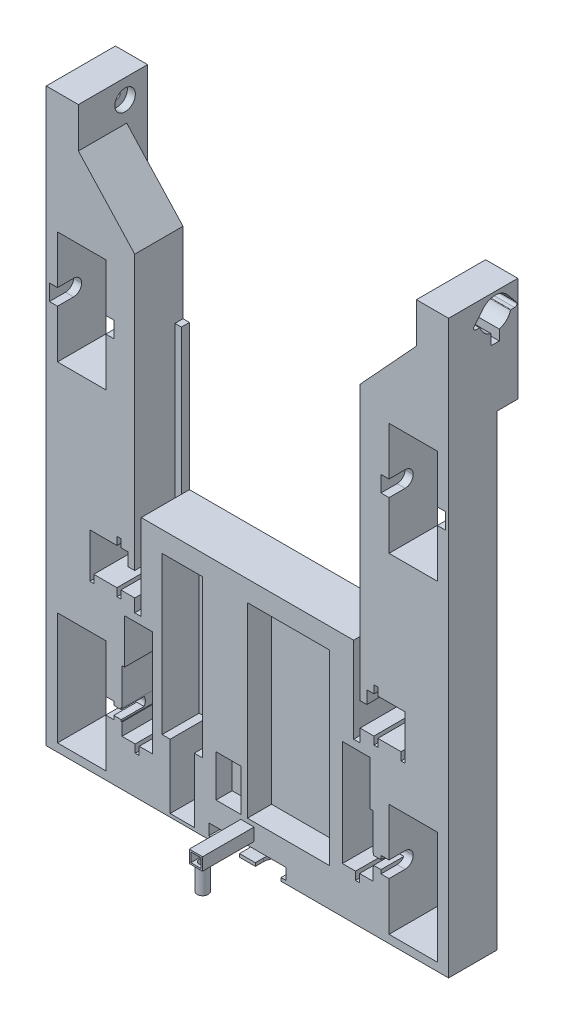
SolidWorks part; units mm, degrees
ref_plane "Front Plane" through (0, 0, 0) normal (0, 0, 1) x (1, 0, 0)
ref_plane "Top Plane" through (0, 0, 0) normal (0, 1, 0) x (1, 0, 0)
ref_plane "Right Plane" through (0, 0, 0) normal (1, 0, 0) x (0, 0, -1)
sketch "Sketch1" plane through (0, 0, 0) normal (0, 0, 1) x (1, 0, 0)
  line L1 (0, 0) -> (250, 0)
  line L8 (0, 0) -> (0, 330)
  line L9 (0, 330) -> (250, 330)
  line L10 (250, 330) -> (250, 0)
  dimension "D1" = 250
  dimension "D2" = 250
  dimension "D3" = 330
extrude "Boss-Extrude2" add sketch "Sketch1" along normal blind 30
sketch "Sketch2" plane through (0, 0, 30) normal (0, 0, 1) x (1, 0, 0)
  line L1 (7, 5) -> (37, 5)
  line L3 (7, 75) -> (37, 75)
  line L4 (37, 5) -> (37, 35)
  line L9 (7, 75) -> (7, 5)
  line L10 (37, 45) -> (42, 45)
  line L12 (37, 35) -> (42, 35)
  line L13 (42, 45) -> (42, 42.675)
  line L14 (42, 37.325) -> (42, 35)
  line L15 (0, 330) -> (0, 0) construction
  line L16 (42, 42.675) -> (46.6, 42.675)
  line L18 (42, 37.325) -> (46.6, 37.325)
  line L19 (46.6, 42.675) -> (46.6, 37.325)
  line L20 (37, 45) -> (37, 75)
  line L21 (7, 40) -> (46.6, 40) construction
  line L22 (0, 0) -> (250, 0) construction
  line L23 (56.55, 94.3) -> (56.55, 23.6) construction
  line L24 (47.1, 28.6) -> (66, 28.6)
  line L25 (47.1, 28.6) -> (47.1, 36.25)
  line L26 (47.1, 66.6) -> (66, 66.6)
  line L27 (66, 28.6) -> (66, 66.6)
  line L28 (48.7, 66.6) -> (66, 66.6)
  line L29 (48.7, 66.6) -> (48.7, 94.3)
  line L30 (48.7, 94.3) -> (66, 94.3)
  line L31 (66, 66.6) -> (66, 94.3)
  line L32 (125, 330) -> (125, 0) construction
  line L33 (55.3, 28.6) -> (57.8, 28.6)
  line L34 (55.3, 28.6) -> (55.3, 23.6)
  line L35 (55.3, 23.6) -> (57.8, 23.6)
  line L36 (57.8, 28.6) -> (57.8, 23.6)
  line L41 (47.1, 43.75) -> (46.6, 43.75)
  line L43 (47.1, 36.25) -> (46.6, 36.25)
  line L44 (47.1, 66.6) -> (47.1, 43.75)
  line L45 (46.6, 43.75) -> (46.6, 36.25)
  line L47 (203.4, 43.75) -> (203.4, 36.25)
  line L48 (202.9, 66.6) -> (202.9, 43.75)
  line L49 (202.9, 36.25) -> (203.4, 36.25)
  line L50 (202.9, 43.75) -> (203.4, 43.75)
  line L51 (192.2, 28.6) -> (192.2, 23.6)
  line L52 (194.7, 23.6) -> (192.2, 23.6)
  line L53 (194.7, 28.6) -> (194.7, 23.6)
  line L54 (194.7, 28.6) -> (192.2, 28.6)
  line L55 (184, 66.6) -> (184, 94.3)
  line L56 (201.3, 94.3) -> (184, 94.3)
  line L57 (201.3, 66.6) -> (201.3, 94.3)
  line L58 (201.3, 66.6) -> (184, 66.6)
  line L60 (202.9, 66.6) -> (184, 66.6)
  line L61 (202.9, 28.6) -> (202.9, 36.25)
  line L62 (202.9, 28.6) -> (184, 28.6)
  line L63 (213, 45) -> (213, 75)
  line L64 (203.4, 42.675) -> (203.4, 37.325)
  line L65 (208, 37.325) -> (203.4, 37.325)
  line L66 (208, 42.675) -> (203.4, 42.675)
  line L67 (208, 37.325) -> (208, 35)
  line L68 (208, 45) -> (208, 42.675)
  line L69 (213, 35) -> (208, 35)
  line L70 (213, 45) -> (208, 45)
  line L71 (243, 75) -> (243, 5)
  line L72 (213, 5) -> (213, 35)
  line L73 (243, 75) -> (213, 75)
  line L74 (243, 5) -> (213, 5)
  line L75 (184, 66.6) -> (184, 28.6)
  line L76 (250, 330) -> (0, 330) construction
  line L77 (0, 165) -> (250, 165) construction
  line L78 (250, 0) -> (250, 330) construction
  line L97 (228, 280) -> (228, 210) construction
  line L101 (37, 280) -> (37, 210)
  line L103 (7, 280) -> (7, 210)
  line L104 (2, 240) -> (7, 240)
  line L105 (2, 250) -> (2, 240)
  line L106 (7, 250) -> (2, 250)
  line L108 (22, 280) -> (22, 210) construction
  line L111 (37, 250) -> (42, 250)
  line L112 (7, 210) -> (37, 210)
  line L113 (7, 280) -> (37, 280)
  line L114 (0, 0) -> (250, 0) construction
  line L115 (101, 9) -> (149, 9)
  line L116 (101, 9) -> (101, 2)
  line L117 (101, 2) -> (149, 2)
  line L118 (149, 9) -> (149, 2)
  line L119 (125, 2) -> (125, 9) construction
  line L120 (101, 5.5) -> (149, 5.5) construction
  line L121 (92, 2) -> (92, 42)
  line L122 (176, 23.5) -> (125, 23.5)
  line L123 (176, 23.5) -> (176, 139.5)
  line L124 (176, 139.5) -> (125, 139.5)
  line L125 (125, 23.5) -> (125, 139.5)
  line L127 (97, 42) -> (97, 139.5)
  line L128 (97, 139.5) -> (72, 139.5)
  line L129 (72, 42) -> (72, 139.5)
  line L132 (77, 42) -> (92, 42)
  line L134 (84.5, 42) -> (84.5, 2) construction
  line L135 (77, 2) -> (92, 2)
  line L136 (72, 42) -> (97, 42)
  line L137 (77, 2) -> (77, 42)
  line L138 (208, 240) -> (213, 240)
  line L139 (120.875, 20.8) -> (129.125, 20.8)
  line L140 (120.875, 20.8) -> (120.875, 13)
  line L141 (120.875, 13) -> (129.125, 13)
  line L142 (129.125, 20.8) -> (129.125, 13)
  line L143 (125, 13) -> (125, 20.8) construction
  line L144 (120.875, 16.9) -> (129.125, 16.9) construction
  line L145 (208, 250) -> (208, 240)
  line L146 (243, 280) -> (213, 280)
  line L147 (243, 210) -> (213, 210)
  line L148 (213, 250) -> (208, 250)
  line L149 (243, 250) -> (248, 250)
  line L153 (248, 250) -> (248, 240)
  line L154 (248, 240) -> (243, 240)
  line L155 (243, 280) -> (243, 210)
  line L157 (42, 250) -> (42, 240)
  line L158 (42, 240) -> (37, 240)
  line L159 (213, 280) -> (213, 210)
  line L169 (46.39, 129.71) -> (50.8, 129.71)
  line L170 (27.05, 129.71) -> (43.93, 129.71)
  line L171 (27.05, 129.71) -> (27.05, 107)
  line L172 (29.54, 107) -> (43.94, 107)
  line L173 (50.8, 129.71) -> (50.8, 121.74)
  line L175 (43.93, 129.71) -> (43.93, 134.62)
  line L176 (43.93, 134.62) -> (46.39, 134.62)
  line L177 (46.39, 129.71) -> (46.39, 134.62)
  line L179 (43.94, 107) -> (43.94, 102.13)
  line L180 (43.94, 102.13) -> (46.4, 102.13)
  line L181 (46.4, 107) -> (46.4, 102.13)
  line L183 (29.54, 107) -> (29.54, 102)
  line L184 (29.54, 102) -> (27.05, 102)
  line L185 (27.05, 107) -> (27.05, 102)
  line L186 (46.4, 107) -> (55, 107)
  line L188 (50.8, 121.74) -> (55, 121.74)
  line L189 (55, 107) -> (55, 121.74)
  line L191 (195, 107) -> (195, 121.74)
  line L192 (199.2, 121.74) -> (195, 121.74)
  line L193 (203.6, 107) -> (195, 107)
  line L194 (222.95, 107) -> (222.95, 102)
  line L195 (220.46, 102) -> (222.95, 102)
  line L196 (220.46, 107) -> (220.46, 102)
  line L197 (203.6, 107) -> (203.6, 102.13)
  line L198 (206.06, 102.13) -> (203.6, 102.13)
  line L199 (206.06, 107) -> (206.06, 102.13)
  line L200 (203.61, 129.71) -> (203.61, 134.62)
  line L201 (206.07, 134.62) -> (203.61, 134.62)
  line L202 (206.07, 129.71) -> (206.07, 134.62)
  line L203 (199.2, 129.71) -> (199.2, 121.74)
  line L204 (220.46, 107) -> (206.06, 107)
  line L205 (222.95, 129.71) -> (222.95, 107)
  line L206 (222.95, 129.71) -> (206.07, 129.71)
  line L207 (203.61, 129.71) -> (199.2, 129.71)
  line L208 (213, 45) -> (213, 35)
  line L209 (121, 23.5) -> (105.5, 23.5)
  line L210 (121, 23.5) -> (121, 49.5)
  line L211 (121, 49.5) -> (105.5, 49.5)
  line L212 (105.5, 23.5) -> (105.5, 49.5)
  line L213 (37, 45) -> (37, 35)
  line L214 (20, 330) -> (55, 292)
  line L215 (2, 292) -> (50, 292)
  line L216 (2, 292) -> (2, 285)
  line L217 (2, 285) -> (50, 285)
  line L218 (50, 292) -> (50, 285)
  line L219 (26, 285) -> (26, 292) construction
  line L220 (2, 288.5) -> (50, 288.5) construction
  line L224 (55, 292) -> (55, 242.25)
  line L225 (55, 242.25) -> (195, 242.25)
  line L226 (230, 330) -> (20, 330)
  line L228 (55, 107) -> (55, 121.74)
  line L231 (230, 330) -> (195, 292)
  line L235 (195, 107) -> (195, 121.74)
  line L236 (195, 292) -> (195, 242.25)
  line L237 (55, 107) -> (55, 99)
  line L238 (55, 242.25) -> (59, 242.25)
  line L239 (55, 242.25) -> (55, 107)
  line L240 (55, 107) -> (59, 107)
  line L241 (59, 242.25) -> (59, 107)
  line L242 (55, 99) -> (59, 99)
  line L243 (59, 99) -> (59, 107)
  line L244 (55, 119.24) -> (59, 119.24)
  line L245 (191, 119.24) -> (195, 119.24)
  line L246 (195, 242.25) -> (195, 107)
  line L247 (191, 242.25) -> (191, 107)
  line L248 (195, 107) -> (191, 107)
  line L249 (191, 99) -> (191, 107)
  line L250 (195, 99) -> (191, 99)
  line L251 (195, 107) -> (195, 99)
  line L252 (0, 311.75) -> (250, 311.75) construction
  line L253 (59, 152.2754) -> (191, 152.2754)
  line L254 (191, 152.2754) -> (191, 242.25)
  line L255 (59, 242.25) -> (59, 152.2754)
  point P26 (56.55, 28.6)
  point P64 (125, 330)
  point P92 (125, 5.5)
  point P101 (2, 245)
  point P110 (84.5, 2)
  point P112 (125, 16.9)
  point P133 (43.93, 132.165)
  point P159 (26, 288.5)
  point P179 (125, 242.25)
  dimension "D1" = 7
  dimension "D2" = 5
  dimension "D3" = 70
  dimension "D5" = 10
  dimension "D6" = 5
  dimension "D7" = 30
  dimension "D8" = 5.35
  dimension "D9" = 4.6
  dimension "D10" = 27.7
  dimension "D11" = 7.5
  dimension "D12" = 0.5
  dimension "D13" = 18.9
  dimension "D14" = 2.5
  dimension "D15" = 3.75
  dimension "D16" = 5
  dimension "D17" = 70.7
  dimension "D18" = 22.85
  dimension "D19" = 17.3
  dimension "D20" = 1.6
  dimension "D21" = 30
  dimension "D22" = 70
  dimension "D23" = 48
  dimension "D24" = 7
  dimension "D25" = 2
  dimension "D26" = 51
  dimension "D27" = 116
  dimension "D28" = 14.5
  dimension "D29" = 25
  dimension "D30" = 97.5
  dimension "D31" = 15
  dimension "D32" = 40
  dimension "D33" = 2
  dimension "D34" = 6
  dimension "D35" = 12.5
  dimension "D36" = 7.8
  dimension "D37" = 8.25
  dimension "D38" = 4
  dimension "D39" = 10
  dimension "D40" = 35
  dimension "D41" = 50
  dimension "D42" = 7
  dimension "D43" = 5
  dimension "D44" = 23.75
  dimension "D45" = 22.71
  dimension "D46" = 5
  dimension "D47" = 2.49
  dimension "D48" = 14.4
  dimension "D49" = 4.87
  dimension "D50" = 2.46
  dimension "D51" = 2.46
  dimension "D52" = 4.91
  dimension "D53" = 16.88
  dimension "D54" = 4.2
  dimension "D55" = 27
  dimension "D56" = 17
  dimension "D57" = 14.74
  dimension "D58" = 26
  dimension "D59" = 15.5
  dimension "D60" = 4
  dimension "D61" = 48
  dimension "D62" = 7
  dimension "D63" = 5
  dimension "D64" = 2
  dimension "D65" = 20
  dimension "D66" = 38
  dimension "D67" = 13
  dimension "D68" = 140
  dimension "D69" = 8
  dimension "D70" = 2.5
  dimension "D71" = 2.5
  dimension "D72" = 18.25
  dimension "D73" = 49.75
sketch "US" plane through (0, 0, 0) normal (0, -1, 0) x (1, 0, 0)
  line L0 (101, 30) -> (149, 30) construction
  line L2 (101, 30) -> (101, 15) construction
  line L3 (101, 15) -> (149, 15) construction
  line L4 (149, 30) -> (149, 15) construction
  line L5 (104.075, 25) -> (104.075, 30)
  line L6 (101, 30) -> (149, 30) construction
  line L7 (120.075, 25) -> (120.075, 30)
  line L8 (125, 30) -> (125, 15) construction
  line L9 (129.925, 25) -> (129.925, 30)
  line L10 (145.925, 25) -> (145.925, 30)
  arc A0 (104.075, 25) -> (120.075, 25) centre (112.075, 25) ccw
  arc A1 (145.925, 25) -> (129.925, 25) centre (137.925, 25) cw
  point P0 (125, 30)
  point P4 (112.075, 17)
  line M10 (250, 30) -> (0, 30)
  dimension "D3" = 16
  dimension "D1" = 48
  dimension "D2" = 15
  dimension "D4" = 2
  dimension "D5" = 25.85
extrude "Boss-Extrude4" add sketch "Sketch2" along normal blind 32 contours L140 L139 L142 L141
sketch "Sketch6" plane through (0, 0, 62) normal (0, 0, 1) x (1, 0, 0)
  line L8 (121.875, 14) -> (128.125, 14)
  line L9 (128.125, 14) -> (128.125, 19.8)
  line L10 (128.125, 19.8) -> (121.875, 19.8)
  line L11 (121.875, 19.8) -> (121.875, 14)
  line L12 (121.875, 14) -> (128.125, 14)
  line L13 (128.125, 14) -> (128.125, 19.8)
  line L14 (128.125, 19.8) -> (121.875, 19.8)
  line L15 (121.875, 19.8) -> (121.875, 14)
  dimension "D1" = 1
extrude "Cut-Extrude1" cut sketch "Sketch6" against normal blind 7
sketch "Sketch7" plane through (0, 13, 0) normal (0, -1, 0) x (1, 0, 0)
  line L0 (120.875, 55) -> (129.125, 55) construction
  line L1 (120.875, 62) -> (120.875, 30) construction
  line L2 (129.125, 62) -> (129.125, 30) construction
  line L3 (120.875, 62) -> (129.125, 62) construction
  circle A0 centre (125, 57.76) radius 2.4
  point P10 (125, 55)
  dimension "D2" = 4.8
  dimension "D1" = 7
  dimension "D3" = 2.76
extrude "Cut-Extrude2" cut sketch "Sketch7" against normal blind 1 contours A0
extrude "Ultrasonic Sensor Eyes" cut sketch "US" against normal blind 2 contours L5 A0 L7 M10 | A1 L10 L9 M10 region at (137.925, 0, 24.2171) region at (112.075, 0, 24.2171)
extrude "Wheel Holes" cut sketch "Sketch2<5>" against normal through all contours L13 L10 L20 L3 L9 L1 L4 L12 L14 | L68 L67 L69 L72 L74 L71 L73 L63 L70 | L146 L159 L147 L155 | L113 L103 L112 L101 region at (22, 40, 30) region at (228, 40, 30) region at (22, 245, 30) region at (228, 245, 30)
sketch "Sketch2<5>" plane through (0, 0, 30) normal (0, 0, 1) x (1, 0, 0) same geometry as "Sketch2"
extrude "Ultrasonic Sensor " cut sketch "Sketch2<6>" against normal blind 15 contours L118 L115 L116 L117 region at (125, 5.5, 30)
sketch "Sketch2<6>" plane through (0, 0, 30) normal (0, 0, 1) x (1, 0, 0) same geometry as "Sketch2"
extrude "Cut-Extrude5" cut sketch "Sketch2<7>" against normal blind 23 contours L129 L136 L132 L127 L128 | L137 L135 L121 L132 region at (84.5, 22, 30) region at (84.5, 90.75, 30)
sketch "Sketch2<7>" plane through (0, 0, 30) normal (0, 0, 1) x (1, 0, 0) same geometry as "Sketch2"
extrude "Cut-Extrude6" cut sketch "Sketch2<9>" against normal blind 15 contours L124 L125 L122 L123
sketch "Sketch2<9>" plane through (0, 0, 30) normal (0, 0, 1) x (1, 0, 0) same geometry as "Sketch2"
extrude "Cut-Extrude7" cut sketch "Sketch2<10>" against normal blind 10 contours L211 L212 L209 L210
sketch "Sketch2<10>" plane through (0, 0, 30) normal (0, 0, 1) x (1, 0, 0) same geometry as "Sketch2"
extrude "Extrude-Thin3" add sketch "Sketch7<5>" along normal blind 15 thin thin type one direction wall 1
sketch "Sketch7<5>" plane through (0, 13, 0) normal (0, -1, 0) x (1, 0, 0) same geometry as "Sketch7"
extrude "Cut-Extrude8" cut sketch "Sketch2<11>" against normal blind 21.25 contours L26 L31 L30 L29 | L41 L45 L19 L43 L25 L24 L27 L26 L44 | L58 L57 L56 L55 | L58 L75 L62 L54 L61 L49 L47 L50 L48 L60 | L53 L54 L51 L52 | L34 L35 L36 L33 region at (56.4996, 47.5605, 30) region at (57.35, 80.45, 30) region at (193.5004, 47.5605, 30) region at (192.65, 80.45, 30) region at (193.45, 26.1, 30)
sketch "Sketch2<11>" plane through (0, 0, 30) normal (0, 0, 1) x (1, 0, 0) same geometry as "Sketch2"
extrude "Cut-Extrude9" cut sketch "Sketch2<12>" against normal blind 15 and the other way through all contours L10 L213 L12 L14 L18 L19 L16 L13 | L208 L70 L68 L66 L47 L65 L67 L69 | L159 L148 L145 L138 | L149 L155 L154 L153 | L103 L106 L105 L104 | L158 L157 L111 L101 region at (41.0833, 40, 30) region at (208.9167, 40, 30) region at (39.5, 245, 30) region at (4.5, 245, 30) region at (210.5, 245, 30) region at (245.5, 245, 30)
sketch "Sketch2<12>" plane through (0, 0, 30) normal (0, 0, 1) x (1, 0, 0) same geometry as "Sketch2"
extrude "Cut-Extrude11" cut sketch "Sketch2<14>" against normal blind 25 contours L186 L189 L239 L188 L173 L169 L177 L176 L175 L170 L171 L185 L184 L183 L172 L179 L180 L181 | L239 L244 L241 L225 | L225 L247 L245 L235 L246 | L200 L207 L203 L192 L235 L191 L193 L197 L198 L199 L204 L196 L195 L194 L205 L206 L202 L201 region at (40.3094, 117.7002, 30) region at (57, 180.745, 30) region at (193, 180.745, 30) region at (209.6906, 117.7002, 30)
sketch "Sketch2<14>" plane through (0, 0, 30) normal (0, 0, 1) x (1, 0, 0) same geometry as "Sketch2"
sketch "Sketch8" plane through (250, 0, 0) normal (1, 0, 0) x (0, 0, -1)
  line L0 (-1.0005, 352.9) -> (-1.0005, 332.0358) construction
  line L7 (-8.5368, 349.4198) -> (-14.1674, 342.556)
  line L8 (-13.0819, 340.2616) -> (-10.7815, 340.2616)
  line L9 (11.0809, 340.2616) -> (8.7804, 340.2616)
  line L12 (19.5, 330) -> (19.5, 355) construction
  line L15 (6.5358, 349.4198) -> (12.1664, 342.556)
  line L16 (-13.0819, 341.6656) -> (-12.7619, 341.6656) construction
  line L17 (-13.0819, 342.4956) -> (-12.7619, 342.4956)
  line L18 (-13.0819, 340.8356) -> (-12.7619, 340.8356)
  line L19 (5.3495, 343) -> (19.5, 343) construction
  line L20 (11.0809, 341.6656) -> (10.7609, 341.6656) construction
  line L21 (11.0809, 342.4956) -> (10.7609, 342.4956)
  line L22 (11.0809, 340.8356) -> (10.7609, 340.8356)
  line L26 (1.4995, 333.4209) -> (1.4995, 327.0358)
  line L27 (1.4995, 327.0358) -> (-3.5005, 327.0358)
  line L28 (-3.5005, 333.4209) -> (-3.5005, 327.0358)
  line L31 (0, 290) -> (13, 290)
  line L32 (13, 293.9869) -> (13, 290)
  line L33 (-30, 330) -> (-30, 355)
  line L34 (-30, 355) -> (13, 355)
  line L35 (13, 355) -> (13, 293.9869)
  line L36 (-30, 330) -> (0, 330)
  line L37 (0, 330) -> (0, 290)
  arc A0 (-10.4383, 340.0103) -> (-10.7815, 340.2616) centre (-10.7815, 339.9016) ccw
  arc A2 (-13.0819, 340.2616) -> (-14.1674, 342.556) centre (-13.0819, 341.6656) cw
  circle A7 centre (-1.0005, 343) radius 2
  arc A8 (6.5358, 349.4198) -> (-8.5368, 349.4198) centre (-1.0005, 343) ccw
  arc A10 (-10.4383, 340.0103) -> (8.4372, 340.0103) centre (-1.0005, 343) ccw
  arc A19 (11.0809, 340.2616) -> (12.1664, 342.556) centre (11.0809, 341.6656) ccw
  arc A20 (8.4372, 340.0103) -> (8.7804, 340.2616) centre (8.7804, 339.9016) cw
  arc A21 (-13.0819, 342.4956) -> (-13.0819, 340.8356) centre (-13.0819, 341.6656) ccw
  arc A22 (-12.7619, 340.8356) -> (-12.7619, 342.4956) centre (-12.7619, 341.6656) ccw
  arc A23 (11.0809, 342.4956) -> (11.0809, 340.8356) centre (11.0809, 341.6656) cw
  arc A24 (10.7609, 340.8356) -> (10.7609, 342.4956) centre (10.7609, 341.6656) cw
  circle A26 centre (-15, 330) radius 34.5 construction
  point P5 (-14.351, 341.0651)
  point P8 (-12.9219, 341.6656)
  point P10 (12.35, 341.0651)
  point P18 (10.9209, 341.6656)
  line M38 (0, 0) -> (0, 330)
  line M39 (0, 330) -> (-30, 330)
  dimension "D1" = 9.9
  dimension "D2" = 9.9
  dimension "D3" = 0.83
  dimension "D6" = 0.36
  dimension "D8" = 1.404
  dimension "D13" = 0.32
  dimension "D12" = 4
  dimension "D15" = 69
  dimension "D16" = 13
  dimension "D18" = 0.65
  dimension "D4" = 8.8778
  dimension "D7" = 2.3004
  dimension "D9" = 26.701
  dimension "D10" = 13
  dimension "D11" = 5
  dimension "D14" = 5
  dimension "D17" = 25
  dimension "D19" = 65
  dimension "D20" = 14.1505
extrude "Boss-Extrude5" add sketch "Sketch8<6>" against normal blind 20 contours A20 A10 L26 L27 L31 L32 L35 L34 L33 L36 L28 A0 L8 A2 L7 A8 L15 A19 L9 M38 M39 | A10 A20 L9 A19 L15 A8 L7 A2 L8 A0 A22 L18 A21 L17 A7 L22 A24 L21 A23 | A10 L28 L27 L26 M39 M38 | L18 A22 L17 A21 | A7 | A24 L22 A23 L21 region at (250, 352.5654, 1.0005) region at (250, 346.4822, 11.9547) region at (250, 330.9345, 0.6206) region at (250, 341.6656, 12.9219) region at (250, 341.6656, -10.9209) region at (250, 343, 1.0005)
sketch "Sketch8<6>" plane through (250, 0, 0) normal (1, 0, 0) x (0, 0, -1) same geometry as "Sketch8"
extrude "Boss-Extrude6" add sketch "Sketch8<7>" against normal blind 20 from offset 230 contours A20 A10 L26 L27 L31 L32 L35 L34 L33 L36 L28 A0 L8 A2 L7 A8 L15 A19 L9 M38 M39 | A10 A20 L9 A19 L15 A8 L7 A2 L8 A0 A22 L18 A21 L17 A7 L22 A24 L21 A23 | A7 | L18 A22 L17 A21 | A24 L22 A23 L21 | A10 L28 L27 L26 M39 M38 | L28 L27 M39 M38 region at (250, 352.5654, 1.0005) region at (250, 346.4822, 11.9547) region at (250, 330.9345, 0.6206) region at (250, 328.5179, 1.7503) region at (250, 341.6656, 12.9219) region at (250, 341.6656, -10.9209) region at (250, 343, 1.0005) offset against normal yes
sketch "Sketch8<7>" plane through (250, 0, 0) normal (1, 0, 0) x (0, 0, -1) same geometry as "Sketch8"
extrude "Cut-Extrude12" cut sketch "Sketch8" against normal blind 15 contours A10 A20 L9 A19 L15 A8 L7 A2 L8 A0 A22 L18 A21 L17 A7 L22 A24 L21 A23 | A10 L28 L27 L26 | L28 L27 M39 M38 region at (250, 352.5654, 1.0005) region at (250, 330.9345, 0.6206) region at (250, 328.5179, 1.7503)
extrude "Cut-Extrude13" cut sketch "Sketch8<4>" against normal blind 18 contours L18 A22 L17 A21 | A24 L22 A23 L21 region at (250, 341.6656, 12.9219) region at (250, 341.6656, -10.9209)
sketch "Sketch8<4>" plane through (250, 0, 0) normal (1, 0, 0) x (0, 0, -1) same geometry as "Sketch8"
extrude "Cut-Extrude14" cut sketch "Sketch8<5>" against normal through all contours A7 region at (250, 343, 1.0005)
sketch "Sketch8<5>" plane through (250, 0, 0) normal (1, 0, 0) x (0, 0, -1) same geometry as "Sketch8"
extrude "Cut-Extrude17" cut sketch "Sketch2<16>" against normal through all contours L214 L224 L225 L236 L231 L226
sketch "Sketch2<16>" plane through (0, 0, 30) normal (0, 0, 1) x (1, 0, 0) same geometry as "Sketch2"
extrude "Extrude-Thin4" add sketch "Sketch2<17>" along normal blind 15 thin contours L215 L218 L217 L216 thin type one direction wall 1
sketch "Sketch2<17>" plane through (0, 0, 30) normal (0, 0, 1) x (1, 0, 0) same geometry as "Sketch2"
sketch "Sketch13" plane through (0, 293, 0) normal (0, 1, 0) x (1, 0, 0)
  line L0 (49, -45) -> (1, -45) construction
  line L1 (49, -45) -> (49, -30) construction
  line L2 (49, -30) -> (1, -30) construction
  line L3 (1, -45) -> (1, -30) construction
  line L4 (45.925, -40) -> (45.925, -45)
  line L5 (49, -45) -> (1, -45) construction
  line L6 (29.925, -40) -> (29.925, -45)
  line L7 (25, -45.6477) -> (25, -30) construction
  line L8 (20.075, -40) -> (20.075, -45)
  line L9 (4.075, -40) -> (4.075, -45)
  line L10 (1, -45) -> (51, -45) construction
  line L11 (1, -45) -> (1, -30) construction
  arc A0 (45.925, -40) -> (29.925, -40) centre (37.925, -40) ccw
  arc A1 (4.075, -40) -> (20.075, -40) centre (12.075, -40) cw
  line M5 (1, -45) -> (51, -45)
  dimension "D2" = 8
  dimension "D1" = 15
  dimension "D3" = 5
  dimension "D4" = 25.85
  dimension "D5" = 48
extrude "Cut-Extrude18" cut sketch "Sketch13" against normal blind 1 contours A1 L9 L8 M5 | L4 A0 L6 M5 region at (12.075, 293, 39.2171) region at (37.925, 293, 39.2171)
fillet "Fillet2" radius 5 12 edges at (39.5, 45, 15) (39.5, 35, 15) (210.5, 35, 15) (210.5, 45, 15) (210.5, 250, 15) (245.5, 250, 15) (245.5, 240, 15) (210.5, 240, 15) (4.5, 240, 15) (4.5, 250, 15) (39.5, 240, 15) (39.5, 250, 15)
extrude "Cut-Extrude19" cut sketch "Sketch2<18>" against normal through all contours L244 L189 L240 L241 | L242 L243 L240 L237 | L248 L191 L245 L247 | L251 L248 L249 L250 region at (57, 113.12, 30) region at (57, 103, 30) region at (193, 113.12, 30) region at (193, 103, 30)
sketch "Sketch2<18>" plane through (0, 0, 30) normal (0, 0, 1) x (1, 0, 0) same geometry as "Sketch2"
sketch "Sketch15" plane through (230, 0, 0) normal (-1, 0, 0) x (0, 0, 1)
  circle A0 centre (1.0005, 343) radius 6.39
  circle A1 centre (1.0005, 343) radius 0.9
  dimension "D1" = 12.78
  dimension "D2" = 1.8
extrude "Cut-Extrude20" cut sketch "Sketch15" against normal blind 5
extrude "Cut-Extrude21" cut sketch "Sketch15<2>" along normal blind 5 from offset 210
sketch "Sketch15<2>" plane through (230, 0, 0) normal (-1, 0, 0) x (0, 0, 1) same geometry as "Sketch15"
sketch "Sketch16" plane through (0, 0, 0) normal (-1, 0, 0) x (0, 0, 1)
  circle A0 centre (1.0005, 343) radius 2
extrude "Cut-Extrude22" cut sketch "Sketch2<19>" against normal through all contours L241 L253 L247 L225 region at (125, 197.2627, 30)
sketch "Sketch2<19>" plane through (0, 0, 30) normal (0, 0, 1) x (1, 0, 0) same geometry as "Sketch2"
sketch "Sketch18" plane through (51, 0, 0) normal (1, 0, 0) x (0, 0, -1)
  line L0 (-45, 293) -> (-30, 293)
  line L1 (-30, 293) -> (-30, 284)
  line L2 (-30, 284) -> (-45, 284)
  line L3 (-45, 284) -> (-45, 293)
extrude "Cut-Extrude23" cut sketch "Sketch18" against normal through all
